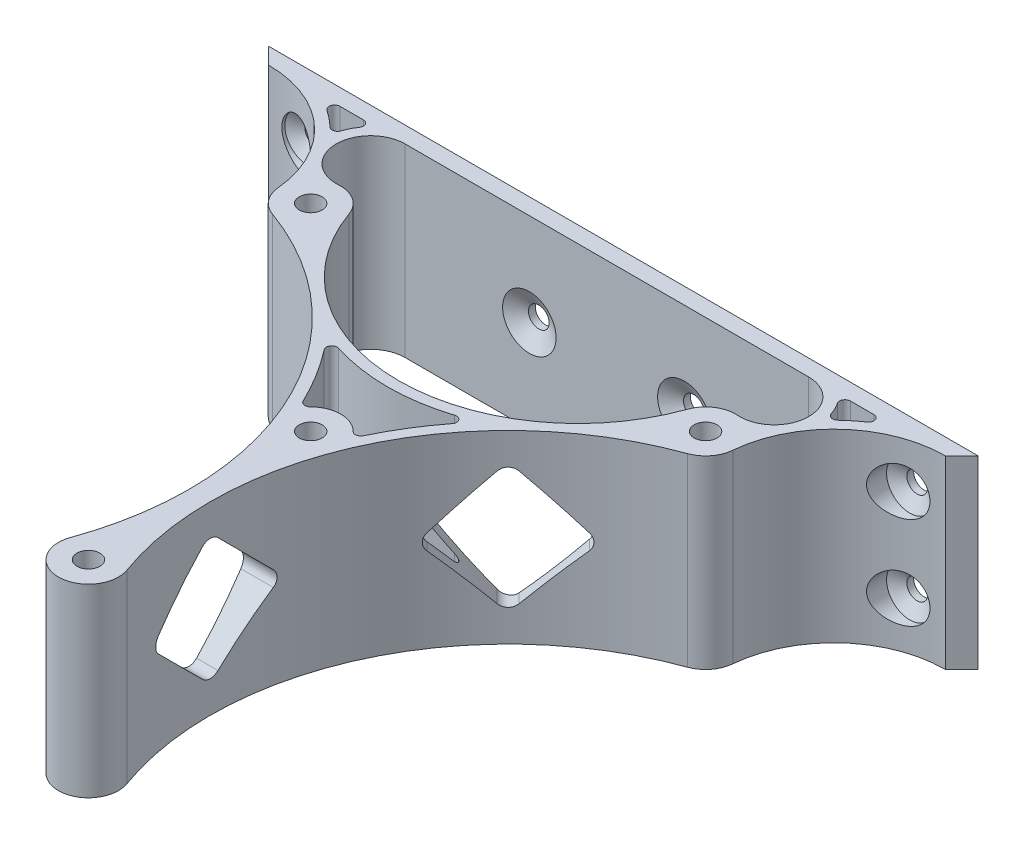
SolidWorks part; units mm, degrees
ref_plane "Front Plane" through (0, 0, 0) normal (0, 0, 1) x (1, 0, 0)
ref_plane "Top Plane" through (0, 0, 0) normal (0, 1, 0) x (1, 0, 0)
ref_plane "Right Plane" through (0, 0, 0) normal (1, 0, 0) x (0, 0, -1)
sketch "Sketch1" plane through (0, 0, 0) normal (0, 0, 1) x (1, 0, 0)
  line L0 (-65, -16.95) -> (65, -16.95) construction
  line L1 (-65, 16.95) -> (65, 16.95) construction
  line L2 (-65, -16.95) -> (65, -16.95)
  line L3 (-65, 16.95) -> (65, 16.95)
sketch "Sketch2" plane through (0, 0, 0) normal (0, 1, 0) x (1, 0, 0)
  line L0 (0, -370) -> (0, 0) construction
  line L3 (-17.6, -175) -> (-17.6, -370)
  line L4 (65, 0) -> (-65, 0)
  line L5 (17.6, -370) -> (17.6, -175)
  line L6 (-17.6, -175) -> (-17.6, -370)
  line L7 (65, 0) -> (-65, 0) construction
  line L8 (17.6, -370) -> (17.6, -175)
  arc A3 (-17.6, -370) -> (17.6, -370) centre (0, -370) ccw
  arc A4 (-17.6, -175) -> (-65, 0) centre (-364.3485, -175) ccw
  arc A5 (65, 0) -> (17.6, -175) centre (364.3485, -175) ccw
  arc A6 (-17.6, -370) -> (17.6, -370) centre (0, -370) ccw
  arc A7 (-17.6, -175) -> (-65, 0) centre (-364.3485, -175) ccw
  arc A8 (65, 0) -> (17.6, -175) centre (364.3485, -175) ccw
  dimension "D1" = 0
sketch "Sketch3" plane through (0, 0, 0) normal (0, 1, 0) x (1, 0, 0)
  line L0 (0, -272.5) -> (-39.2091, 0) construction
  line L1 (-65, 0) -> (65, 0)
  line L2 (-65, 0) -> (-65, -3)
  line L3 (-65, -3) -> (65, -3)
  line L4 (65, 0) -> (65, -3)
  line L5 (0, -370) -> (0, 0) construction
  line L6 (0, -272.5) -> (39.2091, 0) construction
  line L7 (-36.1749, -21.0875) -> (-54.2624, -3) construction
  line L8 (-36.1749, -21.0875) -> (-18.0875, -3) construction
  line L9 (36.1749, -21.0875) -> (18.0875, -3) construction
  line L10 (36.1749, -21.0875) -> (54.2624, -3) construction
  line L11 (0, -21.0875) -> (-18.0875, -3) construction
  line L12 (0, -21.0875) -> (18.0875, -3) construction
  line L13 (17.6, -370) -> (17.6, -175) construction
  line L14 (17.6, -370) -> (17.6, -175) construction
  line L15 (-36.1749, -21.0875) -> (0, -57.2624) construction
  line L16 (0, -57.2624) -> (36.1749, -21.0875) construction
  line L18 (30.9698, -57.2624) -> (0, -97.9824) construction
  line L20 (-30.9698, -57.2624) -> (0, -97.9824) construction
  line L21 (-30.9698, -57.2624) -> (30.9698, -57.2624) construction
  line L22 (0, -21.0875) -> (18.0875, -39.1749) construction
  line L23 (0, -21.0875) -> (-18.0875, -39.1749) construction
  arc A0 (65, 0) -> (17.6, -175) centre (364.3485, -175) ccw construction
  arc A1 (-17.6, -175) -> (-65, 0) centre (-364.3485, -175) ccw construction
  circle A2 centre (-36.1749, -21.0875) radius 2.5 construction
  circle A3 centre (36.1749, -21.0875) radius 2.5 construction
  circle A5 centre (0, -57.2624) radius 2.5 construction
  circle A6 centre (0, -97.9824) radius 2.5 construction
  circle A7 centre (-36.1749, -21.0875) radius 5.5
  circle A9 centre (36.1749, -21.0875) radius 5.5
  circle A10 centre (0, -57.2624) radius 5.5
  circle A11 centre (0, -97.9824) radius 5.5
  point P25 (3.8891, -53.3733)
  point P36 (17.6, -272.5)
  point P39 (32.2858, -24.9765)
  point P40 (-3.8891, -53.3733)
  point P47 (-32.2858, -24.9765)
  point P50 (18.0875, -39.1749)
  point P51 (0, -92.4824)
  point P52 (-18.0875, -39.1749)
  point P57 (0, -62.7624)
  dimension "D2" = 5
  dimension "D1" = 3
  dimension "D3" = 45
  dimension "D4" = 45
  dimension "D5" = 45
  dimension "D6" = 45
  dimension "D7" = 45
  dimension "D8" = 45
  dimension "D9" = 3
sketch "Sketch4" plane through (0, 0, 0) normal (0, 1, 0) x (1, 0, 0)
  line L0 (-56.5349, -77.6224) -> (0, -8.2884) construction
  line L1 (-65, -3) -> (65, -3) construction
  line L2 (-65, 0) -> (-62, -3)
  line L3 (65, 0) -> (62, -3)
  line L4 (-65, 0) -> (65, 0) construction
  line L5 (-36.9719, -3) -> (36.9719, -3)
  line L6 (0, -370) -> (0, 0) construction
  line L7 (-36.9719, -9.3072) -> (-62, -23.4312) construction
  line L8 (-65, 0) -> (65, 0)
  arc A0 (-5.1747, -96.1188) -> (-38.0385, -26.2621) centre (-56.5349, -77.6224) ccw
  arc A1 (38.0385, -26.2621) -> (5.1747, -96.1188) centre (56.5349, -77.6224) ccw
  circle A2 centre (36.1749, -21.0875) radius 5.5 construction
  circle A3 centre (0, -57.2624) radius 5.5 construction
  circle A4 centre (-36.1749, -21.0875) radius 5.5 construction
  circle A5 centre (0, -97.9824) radius 5.5 construction
  arc A6 (-30.9899, -19.2529) -> (30.9899, -19.2529) centre (0, -8.2884) ccw
  arc A7 (-41.6524, -21.5846) -> (-38.0385, -26.2621) centre (-36.1749, -21.0875) ccw
  circle A8 centre (0, -57.2624) radius 5.5 construction
  arc A9 (38.0385, -26.2621) -> (41.6524, -21.5846) centre (36.1749, -21.0875) ccw
  arc A10 (-5.1747, -96.1188) -> (5.1747, -96.1188) centre (0, -97.9824) ccw
  arc A11 (-41.6524, -21.5846) -> (-62, -3) centre (-62, -23.4312) ccw
  arc A12 (62, -3) -> (41.6524, -21.5846) centre (62, -23.4312) ccw
  arc A13 (-36.9719, -3) -> (-36.5461, -15.6) centre (-36.9719, -9.3072) ccw
  arc A14 (36.5461, -15.6) -> (36.9719, -3) centre (36.9719, -9.3072) ccw
  arc A15 (-30.9899, -19.2529) -> (-36.5461, -15.6) centre (-36.1749, -21.0875) ccw
  arc A16 (36.5461, -15.6) -> (30.9899, -19.2529) centre (36.1749, -21.0875) ccw
  point P10 (-20.7736, -33.7649)
  point P11 (-22.0375, -35.3149)
  point P40 (-44.2066, -13.3899)
  point P41 (0, -3)
  point P46 (-42.4648, -12.407)
  dimension "D1" = 2
  dimension "D2" = 45
  dimension "D3" = 2
sketch "Sketch5" plane through (0, 0, 0) normal (0, 1, 0) x (1, 0, 0)
  line L0 (-65, -3) -> (65, -3) construction
  line L1 (-52.7412, -3) -> (-42.3782, -3)
  line L2 (42.3782, -3) -> (52.7412, -3)
  line L4 (36.9719, -3) -> (-36.9719, -3)
  line L5 (36.9719, -3) -> (-36.9719, -3)
  line L8 (-65, 0) -> (-62, -3)
  line L9 (62, -3) -> (65, 0)
  line L10 (65, 0) -> (-65, 0)
  line L11 (-65, 0) -> (-62, -3)
  line L12 (62, -3) -> (65, 0)
  line L13 (65, 0) -> (-65, 0)
  arc A9 (37.3608, -24.3804) -> (3.293, -96.7965) centre (56.5349, -77.6224) ccw
  arc A10 (14.1013, -40.1825) -> (4.828, -54.6279) centre (56.5349, -77.6224) ccw
  circle A11 centre (0, -57.2624) radius 5.5 construction
  arc A12 (-3.293, -96.7965) -> (-37.3608, -24.3804) centre (-56.5349, -77.6224) ccw
  arc A13 (-4.828, -54.6279) -> (-14.1013, -40.1825) centre (-56.5349, -77.6224) ccw
  arc A14 (4.828, -54.6279) -> (-4.828, -54.6279) centre (0, -57.2624) ccw
  arc A17 (-32.8754, -19.92) -> (32.8754, -19.92) centre (0, -8.2884) ccw
  arc A18 (-14.1013, -40.1825) -> (14.1013, -40.1825) centre (0, -8.2884) ccw
  arc A20 (62, -1) -> (39.6606, -21.4038) centre (62, -23.4312) ccw
  arc A21 (52.7412, -3) -> (45.2417, -8.5208) centre (62, -23.4312) ccw
  arc A23 (-39.6606, -21.4038) -> (-62, -1) centre (-62, -23.4312) ccw
  arc A24 (-45.2417, -8.5208) -> (-52.7412, -3) centre (-62, -23.4312) ccw
  arc A26 (-36.9719, -1) -> (-36.4112, -17.5954) centre (-36.9719, -9.3072) ccw
  arc A27 (-42.3782, -3) -> (-45.2417, -8.5208) centre (-36.9719, -9.3072) ccw
  arc A29 (36.4112, -17.5954) -> (36.9719, -1) centre (36.9719, -9.3072) ccw
  arc A30 (45.2417, -8.5208) -> (42.3782, -3) centre (36.9719, -9.3072) ccw
  arc A35 (36.5461, -15.6) -> (36.9719, -3) centre (36.9719, -9.3072) ccw
  arc A36 (36.5461, -15.6) -> (30.9899, -19.2529) centre (36.1749, -21.0875) ccw
  arc A37 (-30.9899, -19.2529) -> (30.9899, -19.2529) centre (0, -8.2884) ccw
  arc A38 (-30.9899, -19.2529) -> (-36.5461, -15.6) centre (-36.1749, -21.0875) ccw
  arc A39 (-36.9719, -3) -> (-36.5461, -15.6) centre (-36.9719, -9.3072) ccw
  arc A40 (36.5461, -15.6) -> (36.9719, -3) centre (36.9719, -9.3072) ccw
  arc A41 (36.5461, -15.6) -> (30.9899, -19.2529) centre (36.1749, -21.0875) ccw
  arc A42 (-30.9899, -19.2529) -> (30.9899, -19.2529) centre (0, -8.2884) ccw
  arc A43 (-30.9899, -19.2529) -> (-36.5461, -15.6) centre (-36.1749, -21.0875) ccw
  arc A44 (-36.9719, -3) -> (-36.5461, -15.6) centre (-36.9719, -9.3072) ccw
  arc A47 (-41.6524, -21.5846) -> (-62, -3) centre (-62, -23.4312) ccw
  arc A48 (-41.6524, -21.5846) -> (-38.0385, -26.2621) centre (-36.1749, -21.0875) ccw
  arc A49 (-5.1747, -96.1188) -> (-38.0385, -26.2621) centre (-56.5349, -77.6224) ccw
  arc A50 (-5.1747, -96.1188) -> (5.1747, -96.1188) centre (0, -97.9824) ccw
  arc A51 (38.0385, -26.2621) -> (5.1747, -96.1188) centre (56.5349, -77.6224) ccw
  arc A52 (38.0385, -26.2621) -> (41.6524, -21.5846) centre (36.1749, -21.0875) ccw
  arc A53 (62, -3) -> (41.6524, -21.5846) centre (62, -23.4312) ccw
  arc A54 (-41.6524, -21.5846) -> (-62, -3) centre (-62, -23.4312) ccw
  arc A55 (-41.6524, -21.5846) -> (-38.0385, -26.2621) centre (-36.1749, -21.0875) ccw
  arc A56 (-5.1747, -96.1188) -> (-38.0385, -26.2621) centre (-56.5349, -77.6224) ccw
  arc A57 (-5.1747, -96.1188) -> (5.1747, -96.1188) centre (0, -97.9824) ccw
  arc A58 (38.0385, -26.2621) -> (5.1747, -96.1188) centre (56.5349, -77.6224) ccw
  arc A59 (38.0385, -26.2621) -> (41.6524, -21.5846) centre (36.1749, -21.0875) ccw
  arc A60 (62, -3) -> (41.6524, -21.5846) centre (62, -23.4312) ccw
  dimension "D1" = 2
  dimension "D2" = 2
  dimension "D3" = 2
  dimension "D4" = 2
  dimension "D5" = 2
  dimension "D6" = 2
  dimension "D7" = 2
  dimension "D8" = 0
  dimension "D9" = 0
extrude "Boss-Extrude1" add sketch "Sketch5" along normal up to surface (16.95 mm away) and the other way up to surface (16.95 mm away)
sketch "Sketch6" plane through (0, 16.95, 0) normal (0, 1, 0) x (1, 0, 0)
  circle A0 centre (36.1749, -21.0875) radius 2.1
  circle A1 centre (-36.1749, -21.0875) radius 2.1
  circle A2 centre (0, -57.2624) radius 2.1
  circle A3 centre (0, -97.9824) radius 2.1
  dimension "D1" = 4.2
extrude "Cut-Extrude1" cut sketch "Sketch6" against normal through all and the other way through all
fillet "Fillet2" radius 1 10 edges at (45.2417, 0, 8.5208) (42.3782, 0, 3) (52.7412, 0, 3) (-42.3782, 0, 3) (-45.2417, 0, 8.5208) (-52.7412, 0, 3) (-14.1013, 0, 40.1825) (14.1013, 0, 40.1825) (4.828, 0, 54.6279) (-4.828, 0, 54.6279)
sketch "Sketch7" plane through (0, 0, 3) normal (0, 0, 1) x (1, 0, 0)
  line L3 (-45.2417, 16.95) -> (-45.2417, -16.95) construction
  line L4 (-65, 16.95) -> (-65, -16.95)
  line L5 (65, 16.95) -> (-65, 16.95)
  line L6 (65, -16.95) -> (65, 16.95)
  line L7 (-65, -16.95) -> (65, -16.95)
  line L8 (-65, 16.95) -> (-65, -16.95) construction
  line L9 (65, 16.95) -> (-65, 16.95) construction
  line L10 (65, -16.95) -> (65, 16.95) construction
  line L11 (-65, -16.95) -> (65, -16.95) construction
  line L12 (-45.2417, 0) -> (-65, 0) construction
  line L13 (-55.1209, 0) -> (-55.1209, 16.95) construction
  line L14 (-55.1209, 0) -> (-55.1209, -16.95) construction
  line L15 (0, -16.95) -> (0, 16.95) construction
  circle A0 centre (-55.1209, 8.475) radius 4.25
  circle A1 centre (-55.1209, -8.475) radius 4.25
  circle A2 centre (55.1209, -8.475) radius 4.25
  circle A3 centre (55.1209, 8.475) radius 4.25
  dimension "D2" = 8.5
  dimension "D1" = 0
extrude "Cut-Extrude2" cut sketch "Sketch7" along normal up to next
sketch "Sketch8" plane through (0, 0, 3) normal (0, 0, 1) x (1, 0, 0)
  circle A0 centre (55.1209, -8.475) radius 1.9
  circle A1 centre (55.1209, 8.475) radius 1.9
  circle A2 centre (-55.1209, -8.475) radius 1.9
  circle A3 centre (-55.1209, 8.475) radius 1.9
  dimension "D1" = 3.8
extrude "Cut-Extrude3" cut sketch "Sketch8" against normal through all
ref_plane "Plane1" through (-24.7421, 0, 24.7421) normal (0.7071, 0, -0.7071) x (-0.7071, 0, -0.7071)
ref_plane "Plane2" through (24.7421, 0, 24.7421) normal (-0.7071, 0, -0.7071) x (-0.7071, 0, 0.7071)
sketch "Sketch10" plane through (24.7421, 0, 24.7421) normal (-0.7071, 0, -0.7071) x (-0.7071, 0, 0.7071)
  line L0 (34.9906, 0) -> (-5.1684, 0) construction
  line L1 (64.3072, 16.95) -> (-8.3271, 16.95) construction
  line L2 (64.3072, 16.95) -> (-8.3271, 16.95) construction
  line L3 (-8.3271, -16.95) -> (64.3072, -16.95) construction
  line L4 (-8.3271, -16.95) -> (64.3072, -16.95) construction
  line L5 (14.9111, -11.95) -> (14.9111, 11.95) construction
  line L6 (14.9111, -11.95) -> (26.8611, 0)
  line L7 (26.8611, 0) -> (14.9111, 11.95)
  line L8 (14.9111, 11.95) -> (2.9611, 0)
  line L9 (2.9611, 0) -> (14.9111, -11.95)
  point P0 (-5.1684, 0)
  point P2 (34.9906, 0)
  point P12 (14.9111, 0)
  point P13 (14.9111, 0)
  point P16 (3.1073, 0)
  dimension "D1" = 5
extrude "Cut-Extrude4" cut sketch "Sketch10" against normal up to next and the other way up to next
mirror "Mirror1" about plane through (0, 0, 0) normal (1, 0, 0) of "Cut-Extrude4"
sketch "Sketch12" plane through (0, 0, 0) normal (1, 0, 0) x (0, 0, -1)
  line L0 (-92.4824, 0) -> (-62.7624, 0) construction
  line L1 (-77.6224, -11.95) -> (-77.6224, 11.95) construction
  line L2 (-35.2858, -11.95) -> (-35.2858, 11.95) construction
  line L7 (-77.6224, -11.95) -> (-89.5724, 0)
  line L8 (-89.5724, 0) -> (-77.6224, 11.95)
  line L9 (-77.6224, 11.95) -> (-65.6724, 0)
  line L10 (-65.6724, 0) -> (-77.6224, -11.95)
  point P6 (-77.6224, 0)
  point P7 (-77.6224, 0)
extrude "Cut-Extrude5" cut sketch "Sketch12" against normal up to next and the other way up to next
sketch "Sketch13" plane through (0, 0, 3) normal (0, 0, 1) x (1, 0, 0)
  line L0 (14.1984, 0) -> (-14.1984, 0) construction
  line L4 (5.7484, 0) -> (14.1984, -11.95)
  line L5 (14.1984, 11.95) -> (5.7484, 0)
  line L6 (22.6483, 0) -> (14.1984, 11.95)
  line L7 (14.1984, -11.95) -> (22.6483, 0)
  line L8 (5.7484, 0) -> (14.1984, -11.95) construction
  line L9 (14.1984, 11.95) -> (5.7484, 0) construction
  line L10 (22.6483, 0) -> (14.1984, 11.95) construction
  line L11 (14.1984, -11.95) -> (22.6483, 0) construction
  circle A0 centre (14.1984, 0) radius 1.9
  circle A1 centre (-14.1984, 0) radius 1.9
  circle A2 centre (55.1209, 8.475) radius 1.9 construction
  point P6 (0, 0)
  point P9 (0, 0)
  dimension "D1" = 0
extrude "Cut-Extrude6" cut sketch "Sketch13" against normal up to next
chamfer "Chamfer1" distance 3 angle 30 6 edges at (-12.2984, 0, 3) (16.0984, 0, 3) (57.0209, 8.475, 3) (57.0209, -8.475, 3) (-53.2209, 8.475, 3) (-53.2209, -8.475, 3)
fillet "Fillet1" radius 2 14 edges at (16.9404, -11.95, 38.0279) (3.9348, 0, 41.9222) (9.6967, 0, 47.684) (16.9404, 11.95, 38.0279) (26.2623, 0, 30.4499) (0, 11.95, 77.6224) (0, 0, 89.5724) (0, 0, 65.6724) (0, -11.95, 77.6224) (-16.9404, -11.95, 38.0279) (-9.6967, 0, 47.684) (-3.9348, 0, 41.9222) (-26.2623, 0, 30.4499) (-16.9404, 11.95, 38.0279)
